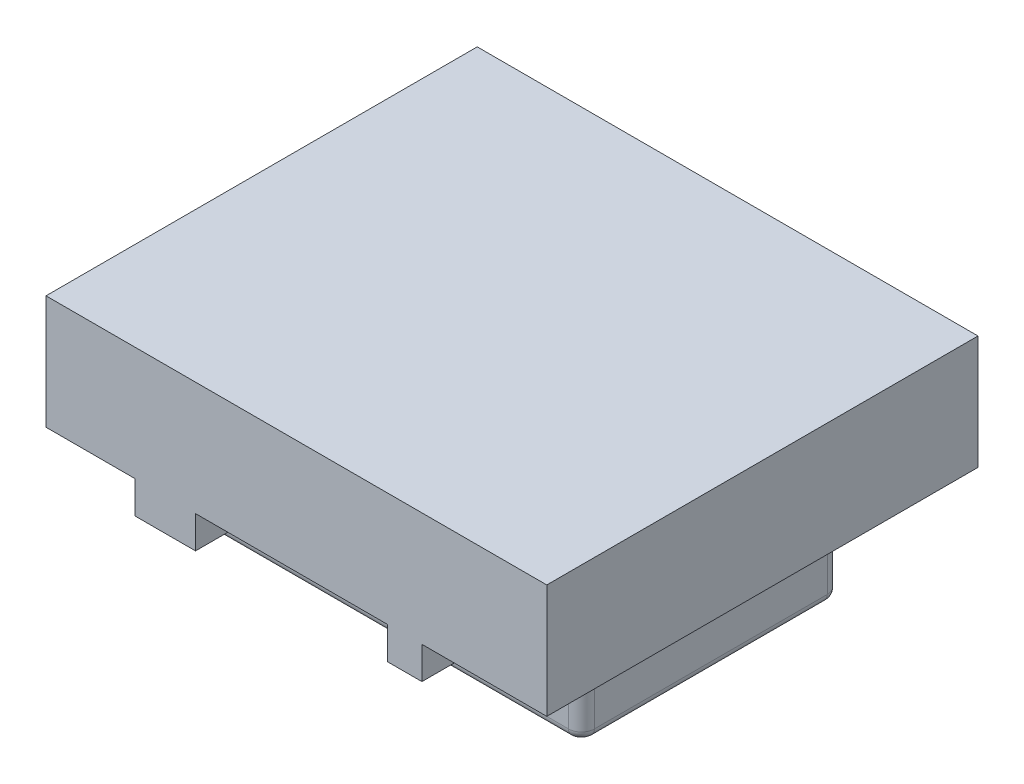
SolidWorks part; units mm, degrees
ref_plane "Front Plane" through (0, 0, 0) normal (0, 0, 1) x (1, 0, 0)
ref_plane "Top Plane" through (0, 0, 0) normal (0, 1, 0) x (1, 0, 0)
ref_plane "Right Plane" through (0, 0, 0) normal (1, 0, 0) x (0, 0, -1)
sketch "Sketch1" plane through (0, 0, 0) normal (0, 1, 0) x (1, 0, 0)
  line L1 (-45, 30) -> (45, 30)
  line L2 (-48, 27) -> (-48, -27)
  line L3 (-45, -30) -> (45, -30)
  line L4 (48, 27) -> (48, -27)
  line L5 (-48, 30) -> (48, -30) construction
  line L6 (-48, -30) -> (48, 30) construction
  arc A0 (-48, -27) -> (-45, -30) centre (-45, -27) ccw
  arc A1 (45, -30) -> (48, -27) centre (45, -27) ccw
  arc A2 (45, 30) -> (48, 27) centre (45, 27) cw
  arc A3 (-45, 30) -> (-48, 27) centre (-45, 27) ccw
  point P0 (0, 0)
  dimension "D3" = 3
  dimension "D1" = 96
  dimension "D2" = 60
extrude "Bottom" add sketch "Sketch1" along normal blind 2.5
extrude "Walls" add sketch "Sketch1<2>" along normal blind 29 thin thin type one direction reverse wall 2.4
sketch "Sketch1<2>" plane through (0, 0, 0) normal (0, 1, 0) x (1, 0, 0) same geometry as "Sketch1"
sketch "Sketch3" plane through (0, 0, 0) normal (0, 1, 0) x (1, 0, 0)
  line L0 (0, 0) -> (0, -22.0538) construction
  line L1 (45, 27.6) -> (-45, 27.6) construction
  circle A0 centre (-42, -15.4) radius 5
  circle A1 centre (42, -15.4) radius 5
  dimension "D1" = 42
  dimension "D2" = 10
  dimension "D3" = 43
extrude "Bolts" add sketch "Sketch3" along normal up to surface (29 mm away) up to face at (0, 29, 0)
extrude "TopCover" add sketch "Sketch1<3>" against normal blind 2.4 from surface starting at face at (0, 29, 0)
sketch "Sketch1<3>" plane through (0, 0, 0) normal (0, 1, 0) x (1, 0, 0) same geometry as "Sketch1"
hole_wizard "CSK for M2.5 Countersunk Flat Head Screw1" positions "Sketch4" profile "Sketch5" countersink size "M2.5" standard "ISO"
sketch "Sketch4" plane through (0, 29, 0) normal (0, 1, 0) x (1, 0, 0)
  point P0 (-42, -15.4)
  point P2 (42, -15.4)
  point P5 (0, 0)
  point P8 (0, 0)
sketch "Sketch5" plane through (-42, 29, 15.4) normal (1, 0, 0) x (0, 0, 1)
  line L0 (0, 0) -> (0, 22.9313)
  line L1 (0, 22.9313) -> (1.55, 22)
  line L2 (1.55, 22) -> (1.55, 1.2)
  line L3 (1.55, 1.2) -> (2.75, 0)
  line L5 (2.75, 0) -> (0, 0)
  line L6 (-1.55, 1.2) -> (-2.75, 0) construction
  line L10 (0, 22.9313) -> (-1.55, 22) construction
  line L11 (0, -6.35) -> (0, 107.95) construction
  dimension "Hole Dia." = 3.1
  dimension "Hole Depth" = 22
  dimension "Near C'Sink Dia." = 5.5
  dimension "Near C'Sink Angle" = 90
  dimension "Drill Angle" = 118
sketch "Sketch6" plane through (-48, 0, 0) normal (-1, 0, 0) x (0, 0, 1)
  line L0 (-27, 0) -> (27, 0) construction
  line L1 (-18.839, 24) -> (5.161, 24)
  line L2 (-18.839, 24) -> (-18.839, 6)
  line L3 (-18.839, 6) -> (5.161, 6)
  line L4 (5.161, 24) -> (5.161, 6)
  line L5 (-18.839, 24) -> (5.161, 6) construction
  line L6 (-18.839, 6) -> (5.161, 24) construction
  point P0 (-6.839, 15)
  point P5 (-6.839, 11.675)
  dimension "D1" = 24
  dimension "D2" = 18
  dimension "D3" = 6
extrude "AC_In" cut sketch "Sketch6" against normal up to next
sketch "Sketch7" plane through (0, 0, 30) normal (0, 0, 1) x (1, 0, 0)
  line L0 (45, 29) -> (45, 0) construction
  line L1 (-12, 22) -> (12, 22)
  line L2 (-12, 22) -> (-12, 7)
  line L3 (-12, 7) -> (12, 7)
  line L4 (12, 22) -> (12, 7)
  line L5 (-12, 22) -> (12, 7) construction
  line L6 (-12, 7) -> (12, 22) construction
  line L7 (-45, 29) -> (45, 29) construction
  circle A0 centre (-28.5, 14.5) radius 7
  circle A1 centre (27, 14.5) radius 4
  circle A2 centre (-16.5, 14.5) radius 1.75
  circle A3 centre (-16.5, 7.2) radius 1.75
  point P8 (0, 0)
  point P9 (0, 0)
  point P10 (0, 14.5)
  point P15 (0, 0)
  point P16 (0, 0)
  point P19 (45, 14.5)
  point P22 (0, 29)
  dimension "D1" = 24
  dimension "D4" = 14
  dimension "D5" = 8
  dimension "D8" = 3.5
  dimension "D2" = 15
  dimension "D3" = 27
  dimension "D6" = 12
  dimension "D7" = 16.5
  dimension "D9" = 7.3
extrude "Control" cut sketch "Sketch7" against normal up to next
fillet "Fillet1" radius 2 16 edges at (47.1213, 0, 29.1213) (0, 0, 30) (-47.1213, 0, 29.1213) (-48, 0, 0) (-47.1213, 0, -29.1213) (0, 0, -30) (47.1213, 0, -29.1213) (47.1213, 29, 29.1213) (0, 29, 30) (-47.1213, 29, 29.1213) (-48, 29, 0) (-47.1213, 29, -29.1213) (0, 29, -30) (47.1213, 29, -29.1213) (48, 0, 0) (48, 29, 0)
sketch "Sketch8" plane through (0, 0, 0) normal (0, 0, 1) x (1, 0, 0)
  line L0 (12, 22) -> (-12, 22) construction
  line L1 (-56.1731, 48.3972) -> (59.9554, 48.3972)
  line L2 (-56.1731, 48.3972) -> (-56.1731, 22)
  line L3 (-56.1731, 22) -> (59.9554, 22)
  line L4 (59.9554, 48.3972) -> (59.9554, 22)
  line L5 (-56.1731, 48.3972) -> (59.9554, 22) construction
  line L6 (-56.1731, 22) -> (59.9554, 48.3972) construction
  point P0 (1.8912, 35.1986)
extrude "Cut1" add sketch "Sketch8" along normal mid plane 100 separate body
sketch "Sketch9" plane through (0, 0, 0) normal (0, 0, 1) x (1, 0, 0)
  line L1 (-35.5, 43.6412) -> (-21.5, 43.6412)
  line L2 (-35.5, 43.6412) -> (-35.5, 14.5)
  line L3 (-35.5, 14.5) -> (-21.5, 14.5)
  line L4 (-21.5, 43.6412) -> (-21.5, 14.5)
  line L5 (-35.5, 43.6412) -> (-21.5, 14.5) construction
  line L6 (-35.5, 14.5) -> (-21.5, 43.6412) construction
  circle A0 centre (-28.5, 14.5) radius 7 construction
  point P0 (-28.5, 29.0706)
  point P8 (0, 0)
extrude "Cut2" add sketch "Sketch9" along normal up to surface (50 mm away) up to face at (1.8912, 35.1986, 50)
sketch "Sketch10" plane through (0, 0, 0) normal (0, 0, 1) x (1, 0, 0)
  line L1 (23, 36.7622) -> (31, 36.7622)
  line L2 (23, 36.7622) -> (23, 14.5)
  line L3 (23, 14.5) -> (31, 14.5)
  line L4 (31, 36.7622) -> (31, 14.5)
  line L5 (23, 36.7622) -> (31, 14.5) construction
  line L6 (23, 14.5) -> (31, 36.7622) construction
  circle A0 centre (27, 14.5) radius 4 construction
  point P0 (27, 25.6311)
  point P5 (27, 14.5)
  point P6 (0, 0)
extrude "Cut3" add sketch "Sketch10" along normal up to surface (50 mm away) up to face at (-13.3044, 26.7243, 50)
fillet "Fillet2" radius 3 4 edges at (-45.6, 14.55, 11.9301) (-45.6, 14.55, 18.8699) (45.6, 14.55, 11.9301) (45.6, 14.55, 18.8699)
